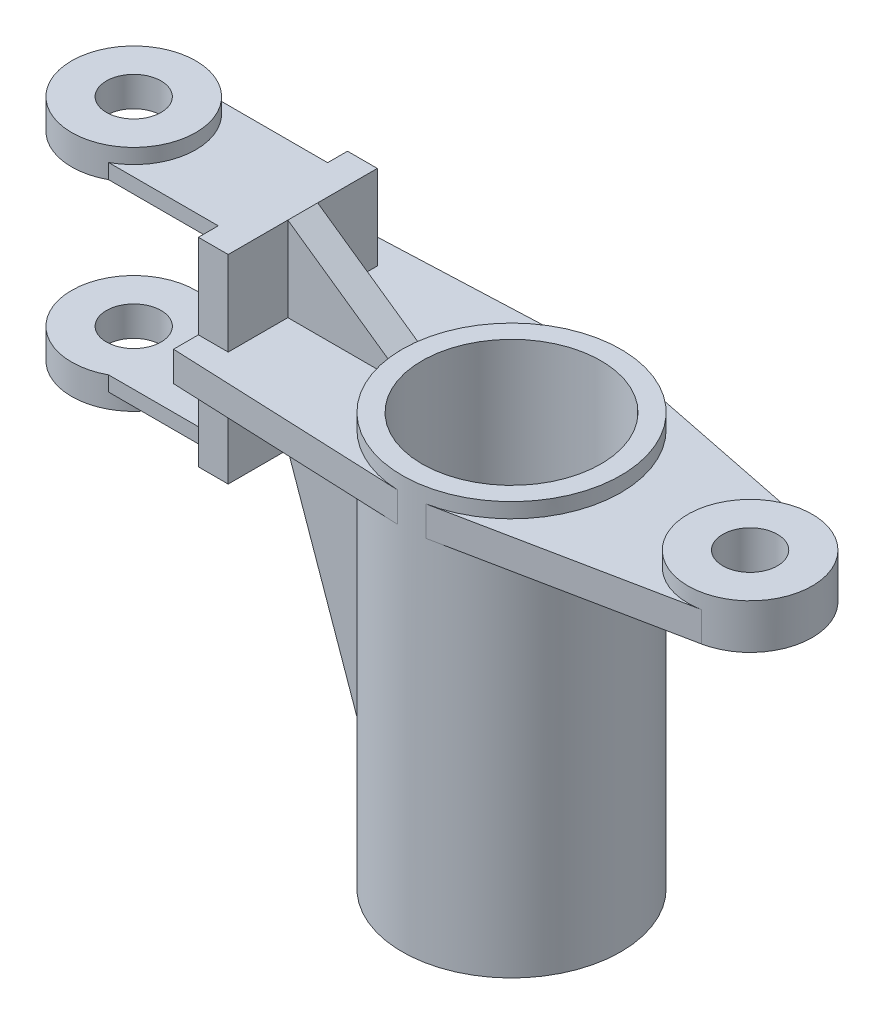
SolidWorks part; units mm, degrees
ref_plane "Front Plane" through (0, 0, 0) normal (0, 0, 1) x (1, 0, 0)
ref_plane "Top Plane" through (0, 0, 0) normal (0, 1, 0) x (1, 0, 0)
ref_plane "Right Plane" through (0, 0, 0) normal (1, 0, 0) x (0, 0, -1)
sketch "Sketch1" plane through (0, 0, 0) normal (0, 1, 0) x (1, 0, 0)
  circle A0 centre (0, 0) radius 22
  circle A1 centre (0, 0) radius 18
  dimension "D1" = 44
  dimension "D2" = 36
extrude "Boss-Extrude1" add sketch "Sketch1" along normal blind 83
sketch "Sketch2" plane through (0, 83, 0) normal (0, 1, 0) x (1, 0, 0)
  line L0 (-48, 20) -> (-48, -20)
  line L1 (0, 0) -> (-91.611, 0) construction
  line L2 (-48, 20) -> (-0.9248, 21.9806)
  line L3 (-48, -20) -> (-0.9248, -21.9806)
  line L4 (4.3542, 21.5648) -> (50.474, 12.2527)
  line L5 (4.3542, -21.5648) -> (50.474, -12.2527)
  circle A0 centre (0, 0) radius 18 construction
  circle A1 centre (0, 0) radius 22 construction
  circle A2 centre (0, 0) radius 18
  arc A3 (-0.9248, -21.9806) -> (4.3542, -21.5648) centre (0, 0) ccw
  arc A4 (50.474, -12.2527) -> (50.474, 12.2527) centre (48, 0) ccw
  circle A5 centre (48, 0) radius 5.5
  arc A6 (4.3542, 21.5648) -> (-0.9248, 21.9806) centre (0, 0) ccw
  point P12 (-48, 0)
  dimension "D1" = 25
  dimension "D2" = 11
  dimension "D3" = 48
  dimension "D4" = 40
  dimension "D5" = 96
extrude "Boss-Extrude2" add sketch "Sketch2" against normal blind 6 from offset 3 offset against normal yes
sketch "Sketch6" plane through (-48, 0, 0) normal (-1, 0, 0) x (0, 0, 1)
  line L1 (-15, 97) -> (15, 97)
  line L2 (-15, 97) -> (-15, 57)
  line L3 (-15, 57) -> (15, 57)
  line L4 (15, 97) -> (15, 57)
  line L6 (21.9806, 80) -> (-21.9806, 80) construction
  line L7 (0, 0) -> (0, 64.7062) construction
  dimension "D1" = 30
  dimension "D2" = 40
  dimension "D3" = 17
extrude "Boss-Extrude5" add sketch "Sketch6" against normal blind 6
sketch "Sketch7" plane through (0, 97, 0) normal (0, 1, 0) x (1, 0, 0)
  line L0 (48, 0) -> (48, -29.8473) construction
  circle A0 centre (-76, 0) radius 12.5
  circle A1 centre (-76, 0) radius 5.5
  dimension "D1" = 25
  dimension "D2" = 11
  dimension "D3" = 124
extrude "Boss-Extrude6" add sketch "Sketch7" along normal blind 6 from offset 3 separate body offset against normal yes
sketch "Sketch8" plane through (0, 97, 0) normal (0, 1, 0) x (1, 0, 0)
  line L0 (-70.0628, 11) -> (-48, 11)
  line L2 (-48, -11) -> (-70.0628, -11)
  line L3 (0, 0) -> (-94.4177, 0) construction
  line L4 (-48, -15) -> (-48, 15) construction
  line L5 (-48, -11) -> (-48, 11)
  circle A0 centre (-76, 0) radius 12.5 construction
  arc A1 (-70.0628, -11) -> (-70.0628, 11) centre (-76, 0) ccw
  point P4 (-104.1784, 27.4618)
  dimension "D1" = 22
extrude "Boss-Extrude7" add sketch "Sketch8" against normal blind 3
ref_plane "Plane1" through (0, 77, 0) normal (0, 1, 0) x (1, 0, 0)
mirror "Mirror3" about plane through (0, 77, 0) normal (0, 1, 0) of "Boss-Extrude7"
sketch "Sketch9" plane through (0, 60, 0) normal (0, 1, 0) x (1, 0, 0)
  circle A0 centre (-76, 0) radius 5.5 construction
  circle A1 centre (-76, 0) radius 12.5 construction
  circle A2 centre (-76, 0) radius 5.5
  circle A3 centre (-76, 0) radius 12.5
extrude "Boss-Extrude8" add sketch "Sketch9" along normal blind 6 from offset 6 offset against normal yes
sketch "Sketch10" plane through (0, 0, 0) normal (0, 0, 1) x (1, 0, 0)
  line L0 (-42, 97) -> (-22, 83)
rib "Rib1" sketch "Sketch10" sketch "Sketch10" thickness 6 extrusion direction parallel to sketch draft on no parameters "D1"=6
sketch "Sketch11" plane through (0, 0, 0) normal (0, 0, 1) x (1, 0, 0)
  line L0 (-42, 57) -> (-22, 0)
  line L1 (-42, 57) -> (-42, 74)
  line L2 (-48, 74) -> (-0.9248, 74) construction
  line L4 (-22, 74) -> (-0.9248, 74) construction
  line L6 (-22, 0) -> (-20, 0)
  line L7 (-20, 0) -> (-20, 74)
  line L8 (-20, 74) -> (-42, 74)
  point P4 (-21.7945, 74)
  point P14 (-22, 74)
  point P15 (-22, 74)
  point P16 (-22.6286, 74)
  point P17 (0, 0)
  point P18 (0, 0)
  dimension "D1" = 2
extrude "Boss-Extrude10" add sketch "Sketch11" along normal mid plane 6
sketch "Sketch12" plane through (0, 80, 0) normal (0, 1, 0) x (1, 0, 0)
  circle A0 centre (48, 0) radius 12.5
  arc A1 (50.474, -12.2527) -> (50.474, 12.2527) centre (48, 0) ccw construction
  circle A2 centre (48, 0) radius 5.5 construction
  circle A3 centre (48, 0) radius 5.5
extrude "Boss-Extrude11" add sketch "Sketch12" along normal blind 3
